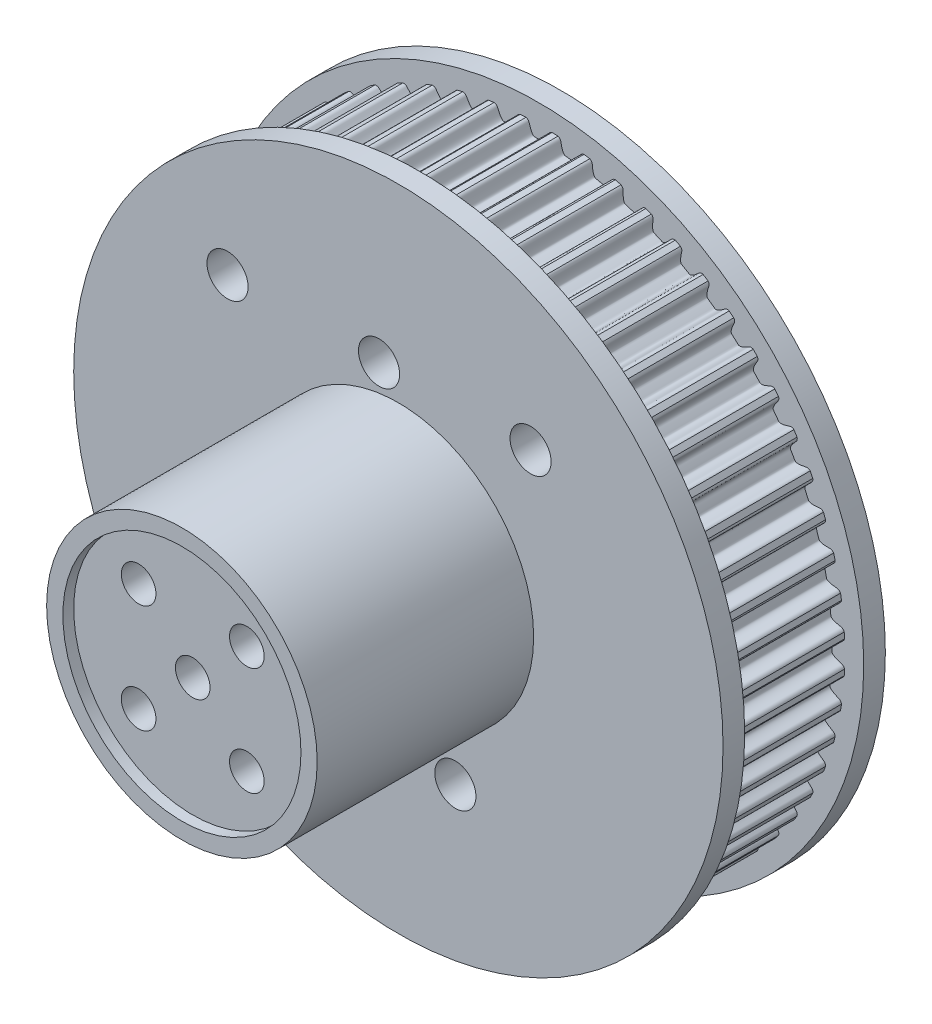
SolidWorks part; units mm, degrees
ref_plane "前视基准面" through (0, 0, 0) normal (0, 0, 1) x (1, 0, 0)
ref_plane "上视基准面" through (0, 0, 0) normal (0, 1, 0) x (1, 0, 0)
ref_plane "右视基准面" through (0, 0, 0) normal (1, 0, 0) x (0, 0, -1)
other "Configuration Table"
ref_axis "基准轴1" through (0, 0, 55) along (0, 0, -1)
sketch "SketchRevolveGearBelt01" plane through (0, 0, 0) normal (1, 0, 0) x (0, 0, -1)
  line L0 (0, 0) -> (1, 0) construction
  line L1 (9.774, 0) -> (9.774, 26.2479)
  line L2 (9.774, 26.2479) -> (9.012, 26.2479)
  line L3 (9.012, 26.2479) -> (9.012, 28.4963)
  line L4 (9.012, 28.4963) -> (9.48, 29.6263)
  line L5 (9.48, 29.6263) -> (8.7761, 29.9179)
  line L6 (8.7761, 29.9179) -> (8.25, 28.6479)
  line L7 (8.25, 28.6479) -> (8.25, 28.2529)
  line L8 (8.25, 28.2529) -> (-8.25, 28.2529)
  line L9 (-8.25, 28.2529) -> (-8.25, 28.6479)
  line L10 (-8.25, 28.6479) -> (-8.7761, 29.9179)
  line L11 (-8.7761, 29.9179) -> (-9.48, 29.6263)
  line L12 (-9.48, 29.6263) -> (-9.012, 28.4963)
  line L13 (-9.012, 28.4963) -> (-9.012, 26.2479)
  line L14 (-9.012, 26.2479) -> (-9.774, 26.2479)
  line L15 (-9.774, 26.2479) -> (-9.774, 0)
  line L16 (-9.774, 0) -> (9.774, 0)
  dimension "GearBeltFlange1OutsideLength" = 2.2484
  dimension "GearBeltFlange1X" = 0.468
  dimension "GearBeltFlange1Y" = 1.13
  dimension "GearBeltFlangeThickness" = 0.762
  dimension "GearBeltFlangeInside" = 0.395
  dimension "GearBeltOutsideDiameter" = 28.2529
  dimension "GearBeltFlange2X" = 0.468
revolve "Gates_PowerGrip_GT_3mm, 15mm Belt Width" add sketch "SketchRevolveGearBelt01" angle 360 about L0
sketch "SketchToothGearBelt01" plane through (0, 0, 0) normal (0, 0, 1) x (1, 0, 0)
  arc A0 (28.2367, 1.2911) -> (28.2367, -1.2911) centre (0, 0) cw
  spline S0 degree 3 poles (28.2367, -1.2911) (28.2364, -1.2655) (28.2322, -1.227) (28.2194, -1.1773) (28.2062, -1.141) (28.1896, -1.1062) (28.1697, -1.0732) (28.1468, -1.0422) (28.121, -1.0136) (28.0925, -0.9876) (28.0617, -0.9645) (28.0288, -0.9444) (27.9942, -0.9274) (27.9308, -0.905) (27.8508, -0.8809) (27.7571, -0.8512) (27.6784, -0.8247) (27.6045, -0.7983) (27.5353, -0.7718) (27.4709, -0.7454) (27.4113, -0.7189) (27.3564, -0.6925) (27.3063, -0.666) (27.2609, -0.6396) (27.2202, -0.6131) (27.1843, -0.5867) (27.1532, -0.5602) (27.1268, -0.5337) (27.1051, -0.5071) (27.0881, -0.4805) (27.0759, -0.4538) (27.0684, -0.4269) (27.0651, -0.3755) (27.0699, -0.3) (27.0701, -0.2) (27.0712, -0.1) (27.0714, 0) (27.0712, 0.1) (27.0701, 0.2) (27.0699, 0.3) (27.0651, 0.3755) (27.0684, 0.4269) (27.0759, 0.4538) (27.0881, 0.4805) (27.1051, 0.5071) (27.1268, 0.5337) (27.1532, 0.5602) (27.1843, 0.5867) (27.2202, 0.6131) (27.2609, 0.6396) (27.3063, 0.666) (27.3564, 0.6925) (27.4113, 0.7189) (27.4709, 0.7454) (27.5353, 0.7718) (27.6045, 0.7983) (27.6784, 0.8247) (27.7571, 0.8512) (27.8508, 0.8809) (27.9308, 0.905) (27.9942, 0.9274) (28.0288, 0.9444) (28.0617, 0.9645) (28.0925, 0.9876) (28.121, 1.0136) (28.1468, 1.0422) (28.1697, 1.0732) (28.1896, 1.1062) (28.2062, 1.141) (28.2194, 1.1773) (28.2322, 1.227) (28.2364, 1.2655) (28.2367, 1.2911) knots 0 0 0 0 0.019513 0.029269 0.039026 0.048782 0.058538 0.068295 0.078051 0.087808 0.097564 0.10732 0.117077 0.126833 0.158411 0.180602 0.201644 0.221544 0.240311 0.257955 0.274488 0.289925 0.304283 0.317585 0.32986 0.341142 0.351478 0.360929 0.369573 0.377512 0.384878 0.391837 0.398582 0.423956 0.449304 0.474652 0.5 0.525348 0.550696 0.576044 0.601418 0.608163 0.615122 0.622488 0.630427 0.639071 0.648522 0.658858 0.67014 0.682415 0.695717 0.710075 0.725512 0.742045 0.759689 0.778456 0.798356 0.819398 0.841589 0.873167 0.882923 0.89268 0.902436 0.912192 0.921949 0.931705 0.941462 0.951218 0.960974 0.970731 0.980487 1 1 1 1
extrude "ToothExtrudeCutGearBelt01" cut sketch "SketchToothGearBelt01" against normal blind 8.25 and the other way blind 8.25
pattern_circular "Tooth Pattern, 60" count 60 every 6 about axis through (0, 0, 55) along (0, 0, -1) of "ToothExtrudeCutGearBelt01"
sketch "BoreRevolveSketch" plane through (0, 0, 0) normal (1, 0, 0) x (0, 0, -1)
  line L0 (0, 0) -> (1, 0) construction
  line L1 (-9.774, 0) -> (9.774, 0)
  line L2 (9.774, 0) -> (9.774, 5)
  line L3 (9.774, 5) -> (-9.774, 5)
  line L4 (-9.774, 5) -> (-9.774, 0)
  dimension "TaperSide1" = 5
  dimension "TaperSide2" = 5
revolve "BoreRevolveCut" cut sketch "BoreRevolveSketch" angle 360 about L0
sketch "AuxiliarySketchGearBelt01" plane through (0, 0, 0) normal (0, 0, 1) x (1, 0, 0)
  circle A0 centre (0, 0) radius 28.6479 construction
  dimension "PitchDiameter" = 57.2958
sketch "草图5" plane through (0, 0, 9.774) normal (0, 0, 1) x (1, 0, 0)
  circle A0 centre (0, 0) radius 34.4314
  dimension "D1" = 68.8628
extrude "切除-拉伸2" cut sketch "草图5" against normal blind 4.55
sketch "草图6" plane through (0, 0, -9.774) normal (0, 0, -1) x (-1, 0, 0)
  circle A0 centre (0, 0) radius 32.2126
extrude "切除-拉伸3" cut sketch "草图6" against normal blind 4
sketch "草图7" plane through (0, 0, 5.224) normal (0, 0, 1) x (1, 0, 0)
  circle A0 centre (0, 0) radius 30
  dimension "D1" = 60
extrude "凸台-拉伸2" add sketch "草图7" along normal blind 2
sketch "草图8" plane through (0, 0, -5.774) normal (0, 0, -1) x (-1, 0, 0)
  circle A0 centre (0, 0) radius 30
extrude "凸台-拉伸3" add sketch "草图8" along normal blind 2
sketch "草图9" plane through (0, 0, 7.224) normal (0, 0, 1) x (1, 0, 0)
  circle A0 centre (0, 0) radius 19.1441
extrude "凸台-拉伸4" add sketch "草图9" against normal blind 14
sketch "草图10" plane through (0, 0, 7.224) normal (0, 0, 1) x (1, 0, 0)
  circle A0 centre (0, 0) radius 12.5
  dimension "D1" = 25
extrude "凸台-拉伸6" add sketch "草图10" along normal blind 20
sketch "草图12" plane through (0, 0, 27.224) normal (0, 0, 1) x (1, 0, 0)
  line L5 (-5, -5) -> (5, 5) construction
  line L6 (-5, 5) -> (5, -5) construction
  circle A0 centre (0, 0) radius 1.6
  circle A1 centre (-5, 5) radius 1.6
  circle A3 centre (5, 5) radius 1.6
  circle A4 centre (5, -5) radius 1.6
  circle A5 centre (-5, -5) radius 1.6
  point P17 (0, 0)
  dimension "D1" = 3.2
  dimension "D4" = 3.2
  dimension "D2" = 10
  dimension "D3" = 10
  dimension "D5" = 4
extrude "切除-拉伸4" cut sketch "草图12" against normal through all
sketch "草图13" plane through (0, 0, 27.224) normal (0, 0, 1) x (1, 0, 0)
  circle A0 centre (0, 0) radius 11
  dimension "D1" = 22
extrude "切除-拉伸5" cut sketch "草图13" against normal blind 1
sketch "草图14" plane through (0, 0, -7.774) normal (0, 0, -1) x (-1, 0, 0)
  circle A0 centre (15.7845, 14.8189) radius 1.9
  circle A1 centre (1.7845, 14.8189) radius 1.9
  circle A2 centre (-12.2155, 14.8189) radius 1.9
  circle A3 centre (-5.2655, -15.4311) radius 1.9
  circle A4 centre (8.7345, -15.4311) radius 1.9
  dimension "D1" = 3.8
  dimension "D2" = 3.8
  dimension "D3" = 3.8
  dimension "D4" = 3.8
  dimension "D5" = 3.8
extrude "切除-拉伸6" cut sketch "草图14" against normal up to next
sketch "草图15" plane through (0, 0, -7.774) normal (0, 0, -1) x (-1, 0, 0)
  circle A0 centre (0, 0) radius 3.5
  circle A1 centre (-5, 5) radius 3
  circle A2 centre (5, 5) radius 3
  circle A3 centre (5, -5) radius 3
  circle A4 centre (-5, -5) radius 3
  point P15 (0, 0)
  dimension "D1" = 7
  dimension "D2" = 6
  dimension "D3" = 4
extrude "切除-拉伸7" cut sketch "草图15" against normal blind 20
